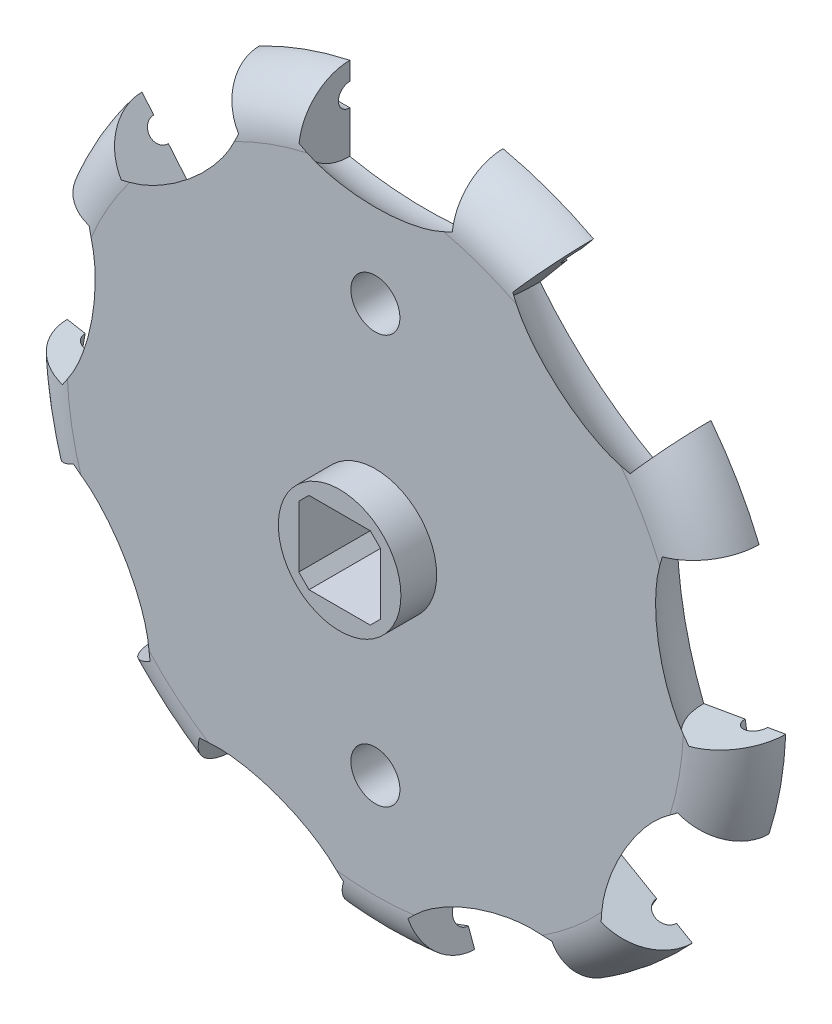
SolidWorks part; units mm, degrees
ref_plane "Front Plane" through (0, 0, 0) normal (0, 0, 1) x (1, 0, 0)
ref_plane "Top Plane" through (0, 0, 0) normal (0, 1, 0) x (1, 0, 0)
ref_plane "Right Plane" through (0, 0, 0) normal (1, 0, 0) x (0, 0, -1)
sketch "Sketch1" plane through (0, 0, 0) normal (0, 0, 1) x (1, 0, 0)
  circle A0 centre (0, 0) radius 27.94
  dimension "D1" = 55.88
extrude "Boss-Extrude1" add sketch "Sketch1" along normal blind 3.9688
fillet "Fillet1" radius 3.9789 1 edges at (27.94, 0, 3.9688)
sketch "Sketch2" plane through (0, 0, 3.9688) normal (0, 0, 1) x (1, 0, 0)
  line L0 (0, 0) -> (0, 27.94) construction
  line L1 (0, 0) -> (0, 7.1566) construction
  line L3 (-3.175, -3.175) -> (3.175, -3.175)
  line L4 (-3.175, -3.175) -> (-3.175, 3.175)
  line L5 (-3.175, 3.175) -> (3.175, 3.175)
  line L6 (3.175, -3.175) -> (3.175, 3.175)
  line L7 (-3.175, -3.175) -> (3.175, 3.175) construction
  line L8 (-3.175, 3.175) -> (3.175, -3.175) construction
  circle A0 centre (0, 15.875) radius 1.905
  circle A1 centre (0, -15.875) radius 1.905
  circle A4 centre (0, 0) radius 27.94 construction
  point P9 (0, 0)
  dimension "D2" = 3.81
  dimension "D4" = 6.35
  dimension "D1" = 15.875
  dimension "D6" = 6.35
  dimension "D3" = 2
extrude "Cut-Extrude1" cut sketch "Sketch2" against normal through all
sketch "Sketch5" plane through (0, 0, 0) normal (0, 0, 1) x (1, 0, 0)
  line L0 (-5.9531, 24.9872) -> (5.9531, 24.9872)
  line L1 (5.9531, 24.9872) -> (5.9531, 29.148)
  line L2 (-5.9531, 24.9872) -> (-5.9531, 29.148)
  line L3 (-5.9531, 24.9872) -> (-8.5086, 24.9872) construction
  arc A0 (-5.9531, 29.148) -> (5.9531, 29.148) centre (0, 0) cw
  circle A1 centre (0, 0) radius 27.94 construction
  point P5 (0, 24.9872)
  point P9 (0, 29.7497)
  dimension "D1" = 11.9062
  dimension "D2" = 24.9872
  dimension "D3" = 9.525
revolve "Cut-Revolve1" cut sketch "Sketch5" angle 360 about L3
sketch "Sketch6" plane through (0, 0, 0) normal (1, 0, 0) x (0, 0, -1)
  line L0 (0, -27.94) -> (0, 27.2984) construction
  circle A0 centre (0, 24.9872) radius 0.889
  arc A1 (-3.9444, 23.663) -> (0, 20.8265) centre (0, 24.9872) ccw construction
  dimension "D1" = 1.778
extrude "Cut-Extrude2" cut sketch "Sketch6" against normal mid plane 15.875
pattern_circular "CirPattern1" count 9 over 360 about axis through (0, 0, 3.9688) along (0, 0, 1) of "Cut-Revolve1", "Cut-Extrude2"
sketch "Sketch7" plane through (0, 0, 3.9688) normal (0, 0, 1) x (1, 0, 0)
  line L5 (3.175, -3.175) -> (3.175, 3.175)
  line L6 (-3.175, -3.175) -> (3.175, -3.175)
  line L7 (-3.175, 3.175) -> (-3.175, -3.175)
  line L8 (3.175, 3.175) -> (-3.175, 3.175)
  line L9 (3.175, -3.175) -> (3.175, 3.175)
  line L10 (-3.175, -3.175) -> (3.175, -3.175)
  line L11 (-3.175, 3.175) -> (-3.175, -3.175)
  line L12 (3.175, 3.175) -> (-3.175, 3.175)
  circle A0 centre (0, 0) radius 4.7625
  dimension "D2" = 9.525
  dimension "D1" = 0
extrude "Boss-Extrude2" add sketch "Sketch7" along normal blind 2.7781
chamfer "Chamfer1" distance 0.7937 angle 45 4 edges at (3.175, -3.175, 3.3734) (-3.175, -3.175, 3.3734) (-3.175, 3.175, 3.3734) (3.175, 3.175, 3.3734)
